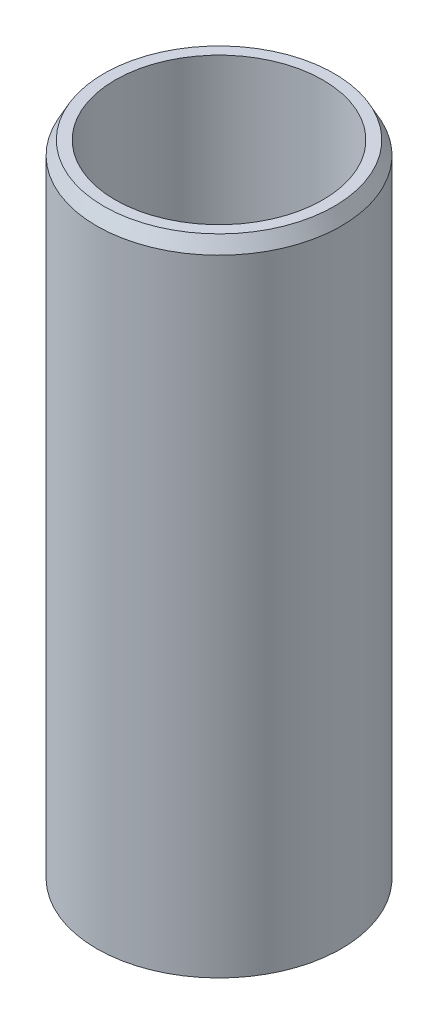
SolidWorks part; units mm, degrees
ref_plane "Front Plane" through (0, 0, 0) normal (0, 0, 1) x (1, 0, 0)
ref_plane "Top Plane" through (0, 0, 0) normal (0, 1, 0) x (1, 0, 0)
ref_plane "Right Plane" through (0, 0, 0) normal (1, 0, 0) x (0, 0, -1)
sketch "Sketch1" plane through (0, 0, 0) normal (0, 1, 0) x (1, 0, 0)
  circle A0 centre (0, 0) radius 50
  dimension "SHAFT_OD" = 100
extrude "Boss-Extrude1" add sketch "Sketch1" along normal blind 264.2787
sketch "Sketch2" plane through (0, 0, 0) normal (0, 1, 0) x (1, 0, 0)
  circle A0 centre (0, 0) radius 42.4554
  dimension "BORE_D" = 84.9108
extrude "Cut-Extrude1" cut sketch "Sketch2" along normal through all
chamfer "Chamfer1" distance 5.4777 angle 28.291 2 edges at (0, 264.2787, 50) (0, 0, 50) first distance on face at (0, 264.2787, 50) first distance on face at (0, 0, 42.4554)
